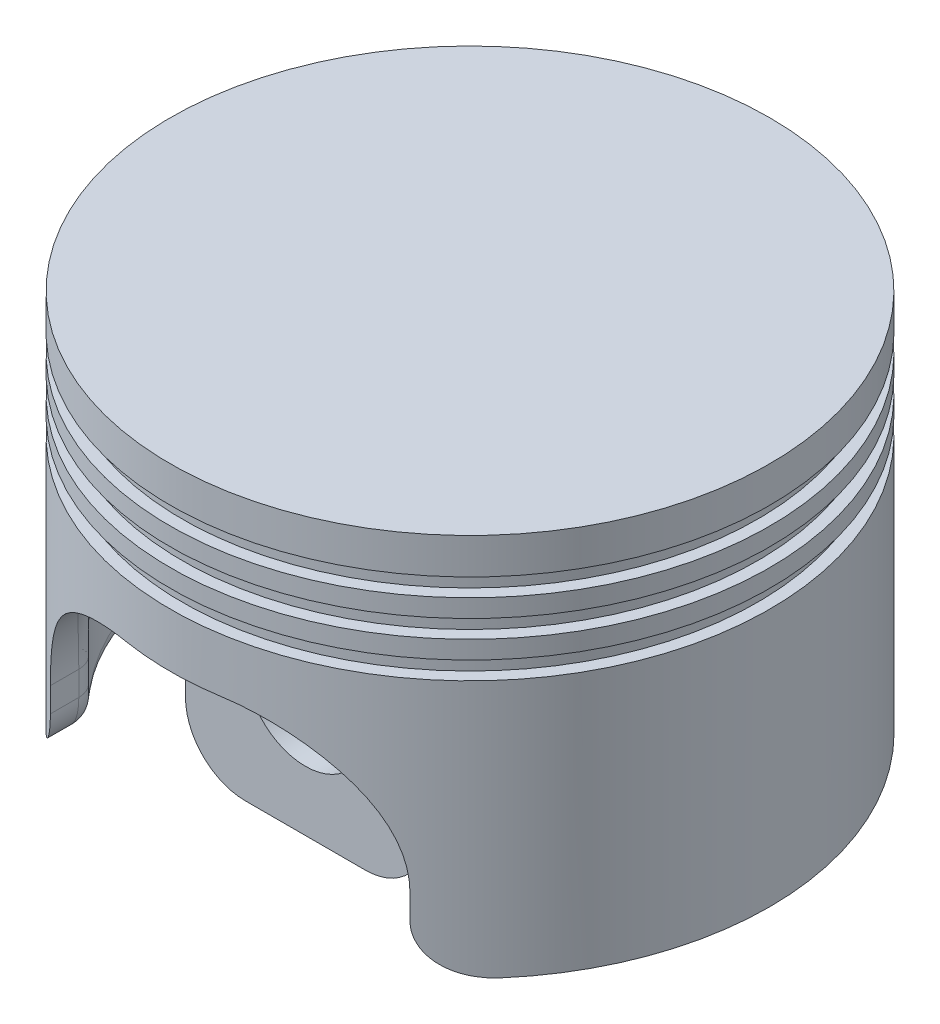
SolidWorks part; units mm, degrees
ref_plane "Front Plane" through (0, 0, 0) normal (0, 0, 1) x (1, 0, 0)
ref_plane "Top Plane" through (0, 0, 0) normal (0, 1, 0) x (1, 0, 0)
ref_plane "Right Plane" through (0, 0, 0) normal (1, 0, 0) x (0, 0, -1)
sketch "Sketch1" plane through (0, 0, 0) normal (1, 0, 0) x (0, 0, -1)
  line L0 (0, 0) -> (63.5, 0)
  line L1 (63.5, 0) -> (63.5, -81.28)
  line L2 (63.5, -81.28) -> (57.15, -81.28)
  line L3 (57.15, -81.28) -> (57.15, -19)
  line L4 (57.15, -19) -> (0, -19)
  line L5 (0, -19) -> (0, 0)
  dimension "D1" = 63.5
  dimension "D2" = 81.28
  dimension "D3" = 6.35
  dimension "D4" = 19
revolve "Revolve1" add sketch "Sketch1" angle 360 about L5
sketch "Sketch2" plane through (0, 0, 0) normal (0, 0, 1) x (1, 0, 0)
  line L0 (63.5, -7.62) -> (60.957, -7.62)
  line L1 (60.957, -7.62) -> (60.957, -11.43)
  line L2 (60.957, -11.43) -> (63.5, -11.43)
  line L3 (63.5, -11.43) -> (63.5, -7.62)
  line L4 (63.5, 0) -> (-63.5, 0) construction
  dimension "D1" = 7.62
  dimension "D2" = 3.81
  dimension "D3" = 2.543
  dimension "D4" = 63.5
ref_axis "Axis1" through (0, -85.344, 0) along (0, 1, 0)
revolve "Cut-Revolve1" cut sketch "Sketch2" angle 360 about axis through (0, -85.344, 0) along (0, 1, 0)
pattern_linear "LPattern1" count 3 spacing 7.62 along (0, -1, 0) of "Cut-Revolve1"
sketch "Sketch3" plane through (0, 0, 0) normal (0, 0, 1) x (1, 0, 0)
  line L0 (0, -85.344) -> (0, 4.064) construction
  line L2 (-38.1, -38.1) -> (38.1, -38.1)
  line L3 (-38.1, -38.1) -> (-38.1, -81.28)
  line L4 (-38.1, -81.28) -> (38.1, -81.28)
  line L5 (38.1, -38.1) -> (38.1, -81.28)
  line L6 (-38.1, -38.1) -> (38.1, -81.28) construction
  line L7 (-38.1, -81.28) -> (38.1, -38.1) construction
  line L8 (63.5, 0) -> (-63.5, 0) construction
  line L9 (-63.5, -81.28) -> (63.5, -81.28) construction
  line L10 (-63.5, -81.28) -> (63.5, -81.28)
  point P2 (0, -59.69)
  dimension "D1" = 76.2
  dimension "D2" = 38.1
extrude "Cut-Extrude1" cut sketch "Sketch3" against normal mid plane 217 contours L5 L2 L3 L4 region at (0, -59.69, 0)
fillet "Fillet1" radius 28 4 edges at (-38.1, -38.1, -46.6985) (38.1, -38.1, -46.6985) (-38.1, -38.1, 46.6985) (38.1, -38.1, 46.6985)
sketch "Sketch4" plane through (0, -19, 0) normal (0, -1, 0) x (1, 0, 0)
  line L5 (-25.4, 34.88) -> (25.4, 34.88)
  line L6 (-25.4, 34.88) -> (-25.4, 15.88)
  line L7 (-25.4, 15.88) -> (25.4, 15.88)
  line L8 (25.4, 34.88) -> (25.4, 15.88)
  line L9 (-25.4, 34.88) -> (25.4, 15.88) construction
  line L10 (-25.4, 15.88) -> (25.4, 34.88) construction
  point P0 (0, 25.38)
  dimension "D1" = 50.8
  dimension "D2" = 19
  dimension "D3" = 15.88
extrude "Boss-Extrude2" add sketch "Sketch4" along normal blind 63.5
mirror "Mirror2" about plane through (0, 0, 0) normal (0, 0, 1) of "Boss-Extrude2"
sketch "Sketch5" plane through (0, 0, 34.88) normal (0, 0, 1) x (1, 0, 0)
  line L0 (25.4, -82.5) -> (-25.4, -82.5) construction
  circle A0 centre (0, -57.1) radius 12.7
  dimension "D1" = 25.4
  dimension "D2" = 25.4
extrude "Cut-Extrude2" cut sketch "Sketch5" against normal mid plane 199.5
fillet "Fillet2" radius 12.7 4 edges at (25.4, -82.5, 25.38) (-25.4, -82.5, 25.38) (-25.4, -82.5, -25.38) (25.4, -82.5, -25.38)
fillet "Fillet3" radius 10 4 edges at (-38.1, -81.28, 46.6985) (-38.1, -81.28, -46.6985) (38.1, -81.28, 46.6985) (38.1, -81.28, -46.6985)
fillet "Fillet4" radius 5 16 edges at (-39.4335, -76.2692, 41.3657) (-38.1, -68.69, 42.5971) (-26.8841, -43.6881, 50.4318) (0, -38.1, 57.15) (33.8387, -51.2516, 46.055) (38.1, -68.69, 42.5971) (40.816, -78.1316, 40.0022) (57.15, -81.28, 0) (39.4335, -76.2692, -41.3657) (38.1, -68.69, -42.5971) (26.8841, -43.6881, -50.4318) (0, -38.1, -57.15) (-33.8387, -51.2516, -46.055) (-38.1, -68.69, -42.5971) (-40.816, -78.1316, -40.0022) (-57.15, -81.28, 0)
